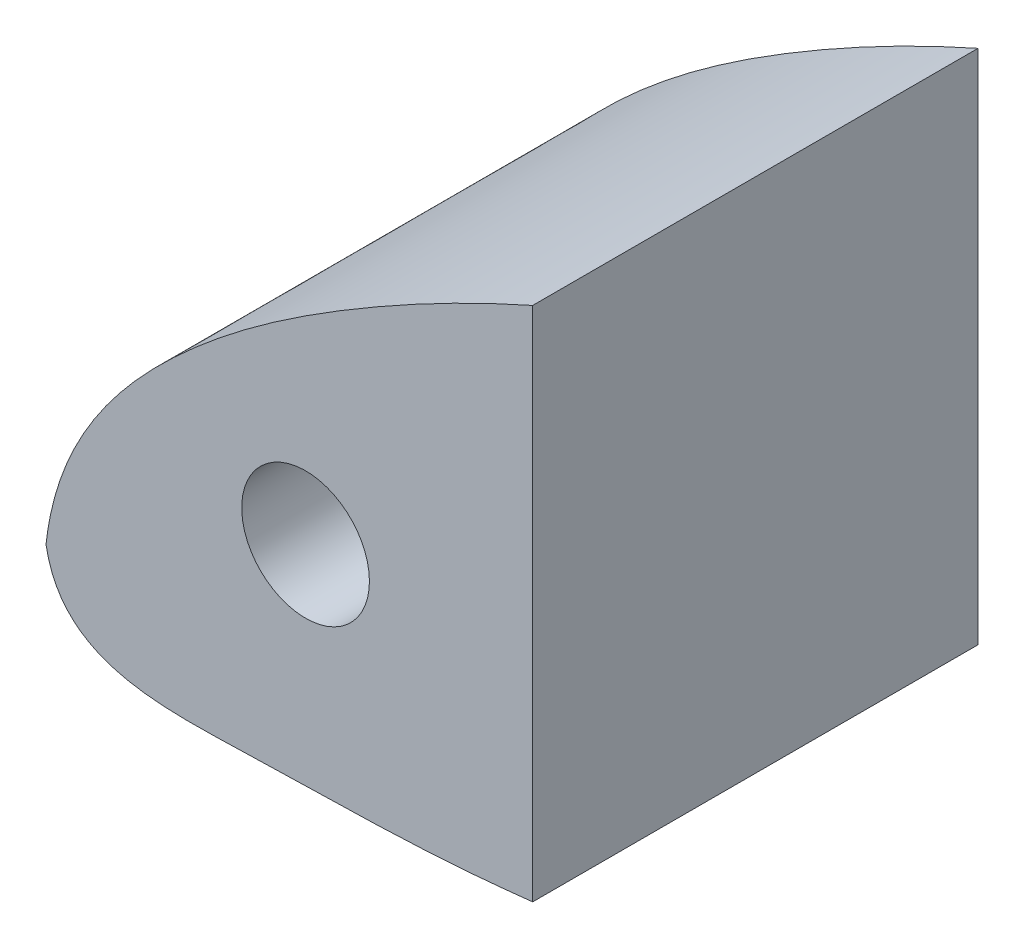
SolidWorks part; units mm, degrees
ref_plane "Front Plane" through (0, 0, 0) normal (0, 0, 1) x (1, 0, 0)
ref_plane "Top Plane" through (0, 0, 0) normal (0, 1, 0) x (1, 0, 0)
ref_plane "Right Plane" through (0, 0, 0) normal (1, 0, 0) x (0, 0, -1)
sketch "Sketch1" plane through (0, 0, 0) normal (0, 0, 1) x (1, 0, 0)
  spline S0 degree 3 poles (0.0006, 0.0001) (0.8106, 7.3592) (8.6491, 17.8566) (26.2867, 29.9752) (52.1111, 42.0692) (89.5976, 49.2908) (131.4008, 47.8848) (173.2567, 40.0411) (217.9611, 29.613) (256.9521, 19.5289) (290.3598, 8.711) (301.2732, 4.3828) (314.8169, -0.5162) (309.8463, 0.0001) knots 0 0 0 0 0.060864 0.113688 0.188609 0.312909 0.448482 0.557612 0.691544 0.852438 0.929756 0.976058 1 1 1 1
  spline S1 degree 3 poles (309.8463, 0.0001) (303.9568, 1.471) (293.9895, 2.094) (276.264, 4.5144) (260.8463, 5.4274) (235.8588, 7.8703) (205.1014, 8.8381) (157.7186, 9.0307) (110.4973, 6.1815) (66.5062, -0.5867) (36.4547, -6.0985) (15.3166, -6.1891) (1.2307, -6.9241) (0.0006, 0.0001) knots 0 0 0 0 0.057787 0.095275 0.171021 0.205339 0.335319 0.464904 0.658702 0.785512 0.893517 0.943092 1 1 1 1
extrude "Boss-Extrude1" add sketch "Sketch1" along normal blind 34.8615
sketch "Sketch2" plane through (0, 0, 34.8615) normal (0, 0, 1) x (1, 0, 0)
  circle A0 centre (20.32, 10.16) radius 5
  circle A1 centre (227.2963, 19.0501) radius 3.175
  dimension "D2" = 10
  dimension "D3" = 6.35
  dimension "D6" = 20.32
  dimension "D1" = 82.55
  dimension "D4" = 19.05
  dimension "D5" = 10.16
extrude "Cut-Extrude1" cut sketch "Sketch2" against normal through all
sketch "Sketch3" plane through (0, 0, 34.8615) normal (0, 0, 1) x (1, 0, 0)
  line L1 (38.1, 71.718) -> (331.2889, 71.718)
  line L2 (38.1, 71.718) -> (38.1, -66.2532)
  line L3 (38.1, -66.2532) -> (331.2889, -66.2532)
  line L4 (331.2889, 71.718) -> (331.2889, -66.2532)
  dimension "D1" = 38.1
extrude "Cut-Extrude2" cut sketch "Sketch3" against normal through all
